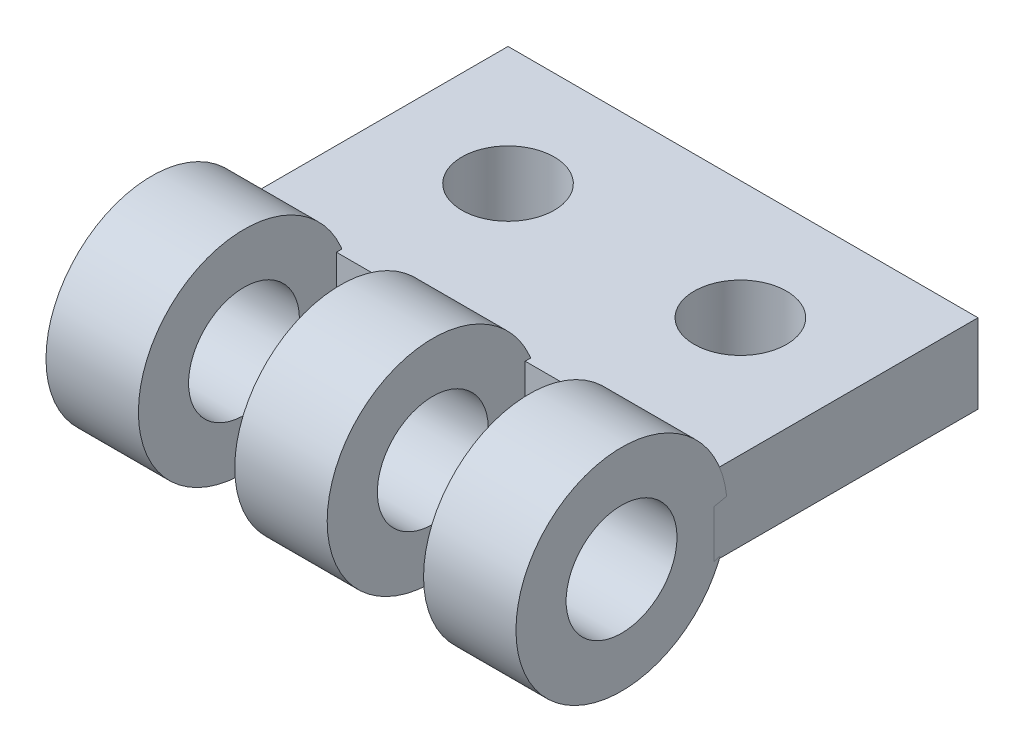
SolidWorks part; units mm, degrees
ref_plane "Alzado" through (0, 0, 0) normal (0, 0, 1) x (1, 0, 0)
ref_plane "Planta" through (0, 0, 0) normal (0, 1, 0) x (1, 0, 0)
ref_plane "Vista lateral" through (0, 0, 0) normal (1, 0, 0) x (0, 0, -1)
sketch "Croquis1" plane through (0, 0, 0) normal (1, 0, 0) x (0, -1, 0)
  circle A0 centre (0, 0) radius 4
  circle A1 centre (0, 0) radius 2.1
  dimension "D1" = 4.2
  dimension "D2" = 8
extrude "Saliente-Extruir1" add sketch "Croquis1" along normal blind 3.5
ref_axis "Eje1" through (3.5, 0, 0) along (-1, 0, 0)
pattern_linear "MatrizL3" count 3 spacing 7.15 along (-1, 0, 0) of bodies 101
ref_plane "Plano1" through (0, 0, -3.5) normal (0, 0, 1) x (1, 0, 0)
ref_plane "Plano2" through (-5.4, 0, 0) normal (1, 0, 0) x (0, 0, -1)
sketch "Croquis4" plane through (0, 0, -3.5) normal (0, 0, 1) x (1, 0, 0)
  line L0 (-5.4, -4.4) -> (-5.4, 4.4) construction
  line L1 (-14.3, 1.5) -> (3.5, 1.5)
  line L2 (-14.3, 1.5) -> (-14.3, -1.5)
  line L3 (-14.3, -1.5) -> (3.5, -1.5)
  line L4 (3.5, 1.5) -> (3.5, -1.5)
  line L5 (-14.3, 4) -> (-14.3, -4) construction
  line L6 (3.5, -4) -> (3.5, 4) construction
  point P4 (-14.3, 0)
  point P6 (-5.4, 1.5)
  dimension "D1" = 3
extrude "Saliente-Extruir2" add sketch "Croquis4" against normal blind 10 separate body
sketch "Croquis5" plane through (0, 1.5, 0) normal (0, 1, 0) x (1, 0, 0)
  line L1 (3.5, 13.5) -> (-14.3, 13.5) construction
  line L2 (3.5, 13.5) -> (3.5, 3.5) construction
  line L3 (-5.4, 13.5) -> (-5.4, 13.9354) construction
  circle A0 centre (-1, 9) radius 1.75
  circle A1 centre (-9.8, 9) radius 1.75
  dimension "D2" = 3.5
  dimension "D1" = 4.5
  dimension "D3" = 4.5
extrude "Cortar-Extruir1" cut sketch "Croquis5" against normal through all
